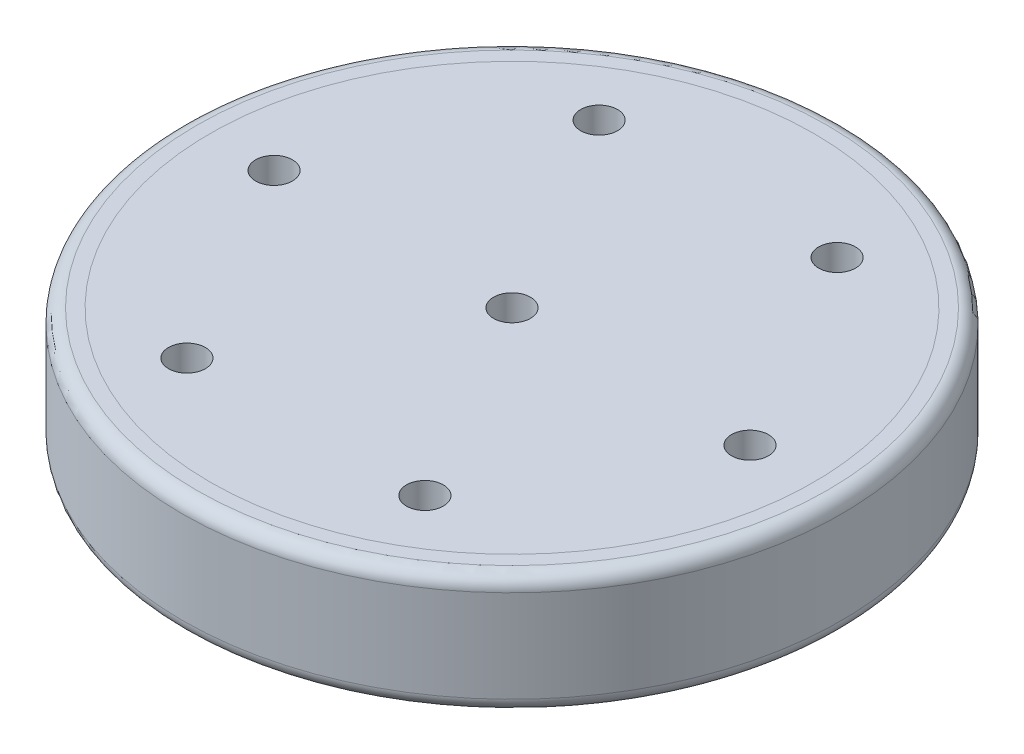
SolidWorks part; units mm, degrees
ref_plane "Alzado" through (0, 0, 0) normal (0, 0, 1) x (1, 0, 0)
ref_plane "Planta" through (0, 0, 0) normal (0, 1, 0) x (1, 0, 0)
ref_plane "Vista lateral" through (0, 0, 0) normal (1, 0, 0) x (0, 0, -1)
sketch "Croquis1" plane through (0, 0, 0) normal (0, 1, 0) x (1, 0, 0)
  circle A0 centre (0, 0) radius 32.75
  dimension "D1" = 65.5
extrude "Saliente-Extruir1" add sketch "Croquis1" along normal blind 3
sketch "Croquis2" plane through (0, 3, 0) normal (0, 1, 0) x (1, 0, 0)
  circle A0 centre (0, 0) radius 2
extrude "Cortar-Extruir1" cut sketch "Croquis2" against normal blind 4
sketch "Croquis7" plane through (0, 3, 0) normal (0, 1, 0) x (1, 0, 0)
  line L2 (25.8141, 0) -> (12.907, 22.3556)
  line L3 (12.907, 22.3556) -> (-12.907, 22.3556)
  line L4 (-12.907, 22.3556) -> (-25.8141, 0)
  line L5 (-25.8141, 0) -> (-12.907, -22.3556)
  line L6 (-12.907, -22.3556) -> (12.907, -22.3556)
  line L7 (12.907, -22.3556) -> (25.8141, 0)
  circle A0 centre (25.8141, 0) radius 2
  circle A4 centre (-25.8141, 0) radius 2
  circle A5 centre (0, 0) radius 22.3556 construction
  circle A6 centre (12.907, 22.3556) radius 2
  circle A7 centre (-12.907, -22.3556) radius 2
  circle A8 centre (-12.907, 22.3556) radius 2
  circle A9 centre (12.907, -22.3556) radius 2
extrude "Cortar-Extruir4" cut sketch "Croquis7" against normal blind 10 contours A8 L4 L3 | A4 L4 L5 | A4 L5 L4 | A8 L3 L4 | L2 A6 L3 | L3 A6 L2 | L7 A0 L2 | L2 A0 L7 | A7 L5 L6 | A7 L6 L5 | L6 A9 L7 | L7 A9 L6 | A4 region at (24.7114, 3, 0) region at (26.3654, 3, 0) region at (12.3557, 3, -21.4007) region at (13.1827, 3, -22.8331) region at (13.1827, 3, 22.8331) region at (12.3557, 3, 21.4007) region at (-12.3557, 3, -21.4007) region at (-13.1827, 3, -22.8331) region at (-13.1827, 3, 22.8331) region at (-12.3557, 3, 21.4007) region at (-24.7114, 3, 0) region at (-26.3654, 3, 0)
sketch "Croquis8" plane through (0, 3, 0) normal (0, 1, 0) x (1, 0, 0)
  circle A0 centre (0, 0) radius 32.75
  circle A1 centre (0, 0) radius 35.75
extrude "Saliente-Extruir2" add sketch "Croquis8" against normal blind 13 separate body
fillet "Redondeo1" radius 1.5 3 edges at (0, -10, 32.75) (0, -10, 35.75) (0, 3, 35.75)
